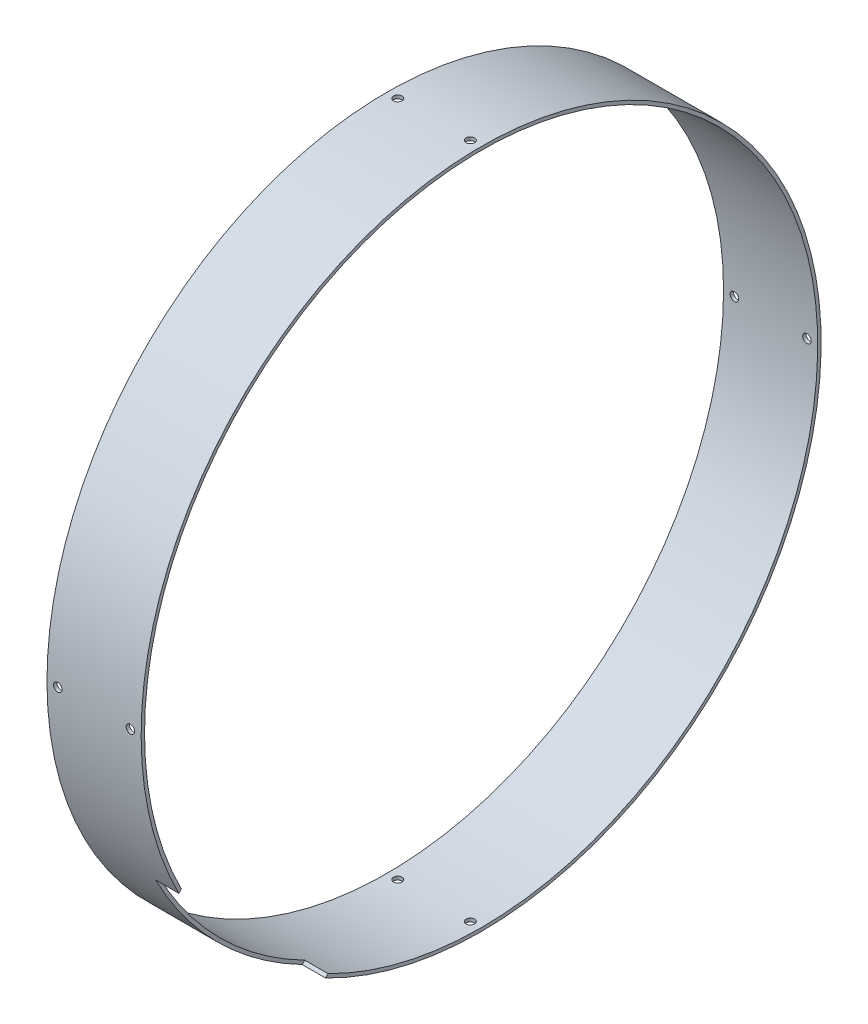
SolidWorks part; units mm, degrees
ref_plane "Front Plane" through (0, 0, 0) normal (0, 0, 1) x (1, 0, 0)
ref_plane "Top Plane" through (0, 0, 0) normal (0, 1, 0) x (1, 0, 0)
ref_plane "Right Plane" through (0, 0, 0) normal (1, 0, 0) x (0, 0, -1)
sketch "Sketch1" plane through (0, 0, 0) normal (1, 0, 0) x (0, 0, -1)
  circle A0 centre (0, 0) radius 100
  circle A1 centre (0, 0) radius 99
  dimension "D1" = 200
  dimension "D2" = 1
extrude "Boss-Extrude1" add sketch "Sketch1" along normal blind 27.7
ref_plane "Plane1" through (0, 0, 100) normal (0, 0, 1) x (1, 0, 0)
hole_wizard "Ø2.5mm Dowel Hole1" positions "Sketch2" profile "Sketch3" hole size "Ø2.5" standard "ANSI Metric" end condition through all
sketch "Sketch2" plane through (0, 0, 100) normal (0, 0, 1) x (1, 0, 0)
  line L0 (27.7, -100) -> (27.7, 100) construction
  line L1 (0, 100) -> (0, -100) construction
  point P0 (24.525, 0)
  point P2 (3.175, 0)
  dimension "D1" = 3.175
  dimension "D2" = 3.175
sketch "Sketch3" plane through (24.525, 0, 100) normal (1, 0, 0) x (0, -1, 0)
  line L0 (0, 0) -> (0, 200)
  line L1 (0, 200) -> (1.25, 200)
  line L2 (1.25, 200) -> (1.25, 0)
  line L5 (1.25, 0) -> (0, 0)
  line L11 (0, -6.35) -> (0, 107.95) construction
  dimension "Thru Hole Dia." = 2.5
  dimension "Thru Hole Depth" = 200
ref_plane "Plane2" through (0, 100, 0) normal (0, 1, 0) x (1, 0, 0)
hole_wizard "Ø2.5mm Dowel Hole2" positions "Sketch4" profile "Sketch5" hole size "Ø2.5" standard "ANSI Metric" end condition through all
sketch "Sketch4" plane through (0, 100, 0) normal (0, 1, 0) x (1, 0, 0)
  line L0 (27.7, -100) -> (27.7, 100) construction
  line L1 (0, 100) -> (0, -100) construction
  point P0 (24.525, 0)
  point P2 (3.175, 0)
  dimension "D1" = 3.175
  dimension "D2" = 3.175
sketch "Sketch5" plane through (24.525, 100, 0) normal (1, 0, 0) x (0, 0, 1)
  line L0 (0, 0) -> (0, 200)
  line L1 (0, 200) -> (1.25, 200)
  line L2 (1.25, 200) -> (1.25, 0)
  line L5 (1.25, 0) -> (0, 0)
  line L11 (0, -6.35) -> (0, 107.95) construction
  dimension "Thru Hole Dia." = 2.5
  dimension "Thru Hole Depth" = 200
ref_plane "Plane3" through (0, 0, 0) normal (0, 0.7071, -0.7071) x (-1, 0, 0)
sketch "Sketch6" plane through (0, 0, 0) normal (0, 0.7071, -0.7071) x (-1, 0, 0)
  line L0 (-21.35, 30) -> (-21.35, -30) construction
  line L1 (-21.35, 30) -> (-27.7, 30) construction
  line L2 (-21.35, -30) -> (-27.7, -30) construction
  line L3 (-27.7, 30) -> (-27.7, -30) construction
  line L5 (-27.7, 100) -> (-27.7, -100) construction
  line L6 (-20.85, 30.5) -> (-28.2, 30.5)
  line L7 (-28.2, 30.5) -> (-28.2, -30.5)
  line L8 (-20.85, -30.5) -> (-28.2, -30.5)
  line L9 (-20.85, 30.5) -> (-20.85, -30.5)
  point P9 (-27.7, 0)
  dimension "D1" = 60
  dimension "D2" = 6.35
  dimension "D3" = 0.5
extrude "Cut-Extrude1" cut sketch "Sketch6" against normal through all
ref_plane "Plane4" through (0, 0, 0) normal (0, 0.7071, 0.7071) x (-1, 0, 0)
sketch "Sketch7" plane through (0, 0, 0) normal (0, 0.7071, 0.7071) x (-1, 0, 0)
  line L0 (-27.7, 7.5) -> (-27.7, -7.5) construction
  line L1 (-27.7, 7.5) -> (-21.35, 7.5) construction
  line L2 (-27.7, -7.5) -> (-21.35, -7.5) construction
  line L3 (-21.35, 7.5) -> (-21.35, -7.5) construction
  line L4 (-27.7, 95.2352) -> (-27.7, -100) construction
  line L5 (-28.2, 8) -> (-20.85, 8)
  line L6 (-20.85, 8) -> (-20.85, -8)
  line L7 (-28.2, -8) -> (-20.85, -8)
  line L8 (-28.2, 8) -> (-28.2, -8)
  point P6 (-21.35, 0)
  dimension "D1" = 6.35
  dimension "D2" = 15
  dimension "D3" = 0.5
extrude "Cut-Extrude2" [suppressed] cut sketch "Sketch7" against normal through all both and the other way through all
